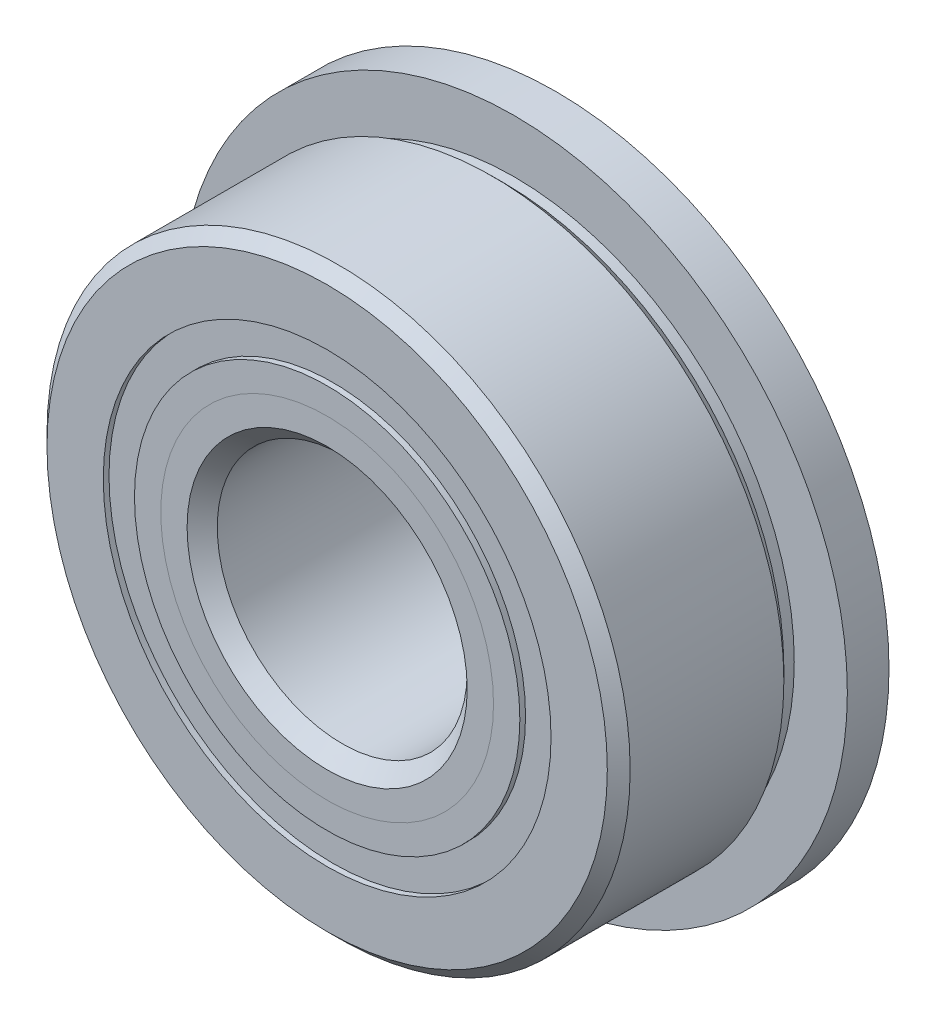
SolidWorks part; units mm, degrees
ref_plane "Front Plane" through (0, 0, 0) normal (0, 0, 1) x (1, 0, 0)
ref_plane "Top Plane" through (0, 0, 0) normal (0, 1, 0) x (1, 0, 0)
ref_plane "Right Plane" through (0, 0, 0) normal (1, 0, 0) x (0, 0, -1)
sketch "Sketch1" plane through (0, 0, 0) normal (1, 0, 0) x (0, 0, -1)
  line L0 (-4.3561, 0) -> (4.3561, 0) construction
  line L1 (0, 11.1125) -> (0, -11.1125) construction
  line L2 (3.9205, 11.1125) -> (-3.9205, 11.1125)
  line L3 (-3.9205, 11.1125) -> (-4.3561, 10.6769)
  line L4 (-4.3561, 10.6769) -> (-4.3561, 8.5315)
  line L5 (-4.3561, 8.5315) -> (-1.936, 8.5315)
  line L6 (4.3561, 8.5315) -> (1.936, 8.5315)
  line L7 (4.3561, 10.6769) -> (4.3561, 8.5315)
  line L8 (3.9205, 11.1125) -> (4.3561, 10.6769)
  line L9 (0, 11.1125) -> (0, 7.9375) construction
  line L10 (0, 7.9375) -> (0, 4.7625) construction
  line L11 (4.3561, 0) -> (5.9627, 0) construction
  arc A0 (-1.936, 8.5315) -> (1.936, 8.5315) centre (0, 7.9375) cw
  point P14 (0, 4.7625)
  dimension "D3" = 3.8721
  dimension "D1" = 45
  dimension "Width" = 8.7122
  dimension "OD" = 22.225
  dimension "D2" = 0.4356
  dimension "Shaft Dia" = 9.525
  dimension "D4" = 0.594
  dimension "Total Wd" = 10.3187
revolve "Revolve1" add sketch "Sketch1" angle 360 about L0
sketch "Sketch2" plane through (0, 0, 0) normal (1, 0, 0) x (0, 0, -1)
  line L0 (-4.3561, 7.3435) -> (-1.936, 7.3435)
  line L1 (-4.3561, 10.6769) -> (-4.3561, -10.6769) construction
  line L2 (-4.3561, 7.3435) -> (-4.3561, 6.3405)
  line L3 (-4.3561, 6.3405) -> (-3.3531, 5.3374)
  line L4 (-3.3531, 5.3374) -> (0, 5.3374)
  line L5 (0, 11.1125) -> (0, -11.1125) construction
  line L6 (0, 5.3374) -> (0, 5.9124)
  line L7 (0, 5.9124) -> (0, 4.7625) construction
  line L8 (-4.3561, 7.3435) -> (-4.3561, 5.3374) construction
  line L9 (-4.3561, 5.3374) -> (-3.3531, 5.3374) construction
  arc A0 (-1.936, 7.3435) -> (0, 5.9124) centre (0, 7.9375) ccw
  arc A1 (1.936, 8.5315) -> (-1.936, 8.5315) centre (0, 7.9375) ccw construction
  circle A2 centre (0, 7.9375) radius 2.0251 construction
  dimension "D1" = 45
revolve "Revolve2" add sketch "Sketch2" angle 360 about L0
sketch "Sketch3" plane through (0, 0, 0) normal (1, 0, 0) x (0, 0, -1)
  line L0 (-4.3561, 6.3405) -> (-3.3531, 5.3374)
  line L1 (-3.3531, 5.3374) -> (0, 5.3374)
  line L2 (0, 5.3374) -> (0, 5.9124)
  line L3 (-4.3561, 6.3405) -> (-4.3561, 5.3374)
  line L4 (-4.3561, 7.3435) -> (-4.3561, 5.3374) construction
  line L5 (-4.3561, 5.3374) -> (-3.7812, 4.7625)
  line L6 (-3.7812, 4.7625) -> (5.527, 4.7625)
  line L8 (5.527, 4.7625) -> (5.9627, 5.1981)
  line L10 (5.9627, 5.1981) -> (5.9627, 7.3435)
  line L11 (5.9627, 7.3435) -> (1.936, 7.3435)
  line L13 (3.9205, 11.1125) -> (4.3561, 10.6769) construction
  circle A0 centre (0, 7.9375) radius 2.0251 construction
  arc A1 (1.936, 7.3435) -> (0, 5.9124) centre (0, 7.9375) cw
revolve "Revolve3" add sketch "Sketch3" angle 360 about L0
sketch "Sketch5" plane through (0, 0, 0) normal (1, 0, 0) x (0, 0, -1)
  line L0 (4.3561, 10.6769) -> (4.3561, 8.5315) construction
  line L1 (4.3561, 9.6042) -> (2.7686, 9.6042)
  line L2 (4.3561, 9.6042) -> (4.3561, 12.7)
  line L3 (4.3561, 12.7) -> (2.7686, 12.7)
  line L4 (2.7686, 9.6042) -> (2.7686, 12.7)
  line L5 (5.9627, 0) -> (-4.3561, 0) construction
  dimension "D1" = 1.5875
  dimension "Flange OD" = 25.4
revolve "Revolve5" add sketch "Sketch5" angle 360 about L5
sketch "Sketch6" plane through (0, 0, 0) normal (1, 0, 0) x (0, 0, -1)
  line L0 (1.9361, 11.1125) -> (2.3717, 10.6769)
  line L1 (3.9205, 11.1125) -> (-3.9205, 11.1125) construction
  line L2 (2.3717, 10.6769) -> (2.7686, 10.6769)
  line L3 (2.7686, 10.6769) -> (2.7686, 11.1125)
  line L4 (2.7686, 11.1125) -> (1.9361, 11.1125)
  line L5 (3.9205, 11.1125) -> (4.3561, 10.6769) construction
  line L6 (2.7686, 9.6042) -> (2.7686, 12.7) construction
  dimension "D1" = 0.3969
revolve "Cut-Revolve1" cut sketch "Sketch6" angle 360 about L0
sketch "Sketch4" plane through (0, 0, 0) normal (1, 0, 0) x (0, 0, -1)
  line L0 (-2.0251, 7.9375) -> (2.0251, 7.9375)
  circle A1 centre (0, 7.9375) radius 2.0251 construction
  arc A2 (-2.0251, 7.9375) -> (2.0251, 7.9375) centre (0, 7.9375) cw
  arc A3 (1.936, 8.5315) -> (-1.936, 8.5315) centre (0, 7.9375) ccw construction
revolve "Revolve4" add sketch "Sketch4" angle 360 about L0
ref_axis "Axis1" through (0, 0, -4.3561) along (0, 0, 1)
pattern_circular "CirPattern1" count 12 every 30 about axis through (0, 0, -4.3561) along (0, 0, 1) of bodies 104
sketch "Sketch7" plane through (0, 0, 0) normal (1, 0, 0) x (0, 0, -1)
  line L0 (-4.3561, 8.5315) -> (-1.936, 8.5315) construction
  line L1 (-4.1383, 8.5315) -> (-2.0251, 8.5315)
  line L2 (-4.1383, 8.5315) -> (-4.1383, 7.3435)
  line L3 (-4.1383, 7.3435) -> (-2.0251, 7.3435)
  line L4 (-2.0251, 8.5315) -> (-2.0251, 7.3435)
  line L5 (-4.3561, 7.3435) -> (-1.936, 7.3435) construction
  line L6 (-3.9205, 11.1125) -> (-4.3561, 10.6769) construction
  line L7 (4.3561, 8.5315) -> (1.936, 8.5315) construction
  line L8 (4.1383, 8.5315) -> (2.0251, 8.5315)
  line L9 (4.1383, 8.5315) -> (4.1383, 7.3435)
  line L10 (4.1383, 7.3435) -> (2.0251, 7.3435)
  line L11 (2.0251, 8.5315) -> (2.0251, 7.3435)
  line L12 (5.9627, 7.3435) -> (1.936, 7.3435) construction
  line L13 (3.9205, 11.1125) -> (4.3561, 10.6769) construction
  circle A0 centre (0, 7.9375) radius 2.0251 construction
  point P10 (-4.1383, 10.8947)
  point P21 (4.1383, 10.8947)
revolve "Revolve6" add sketch "Sketch7" angle 360 about L0
equation "\"D2@Sketch1\" = \"Width@Sketch1\"*.05"
equation "\"D3@Sketch1\" = \"Width@Sketch1\"/2.25"
equation "\"D4@Sketch1\" = (((\"OD@Sketch1\"-\"Width@Sketch1\")/2)/3.25)/3.5"
equation "\"D2@CirPattern1\" = 360/\"Balls@CirPattern1\""
